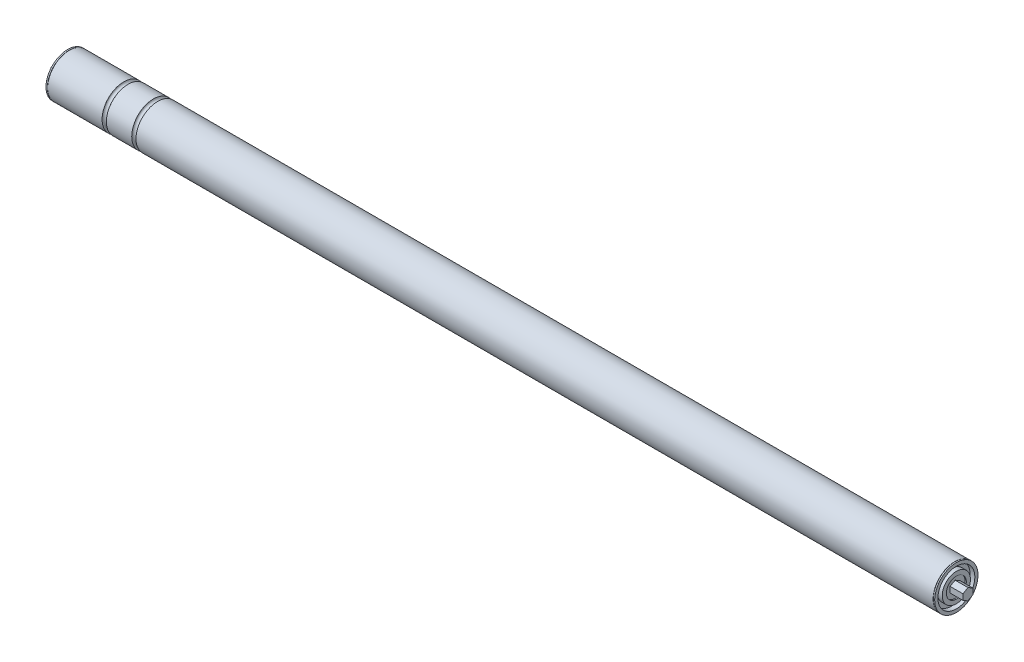
SolidWorks part; units mm, degrees
ref_plane "Front Plane" through (0, 0, 0) normal (0, 0, 1) x (1, 0, 0)
ref_plane "Top Plane" through (0, 0, 0) normal (0, 1, 0) x (1, 0, 0)
ref_plane "Right Plane" through (0, 0, 0) normal (1, 0, 0) x (0, 0, -1)
sketch "Sketch1" plane through (0, 0, 0) normal (0, 0, 1) x (1, 0, 0)
  line L0 (-493.7125, 0) -> (493.7125, 0) construction
  line L1 (493.7125, 0) -> (508, 0) construction
  line L2 (-493.7125, 0) -> (-508, 0) construction
  line L3 (0, 24.13) -> (0, -24.13) construction
  line L4 (-508, 5.5562) -> (-508, -5.5563) construction
  line L5 (508, 5.5562) -> (508, -5.5562) construction
  line L6 (-495.0969, 24.13) -> (-495.0969, -24.13) construction
  line L7 (-495.0969, 0) -> (495.0969, 0) construction
  line L8 (495.0969, 24.13) -> (495.0969, -24.13) construction
  line L9 (-430.2125, 24.13) -> (-430.2125, -24.13) construction
  line L10 (-432.5937, 21.7188) -> (-427.8312, 21.7188) construction
  line L11 (-495.3, 11.1125) -> (-495.3, -11.1125) construction
  line L12 (495.3, 11.1125) -> (495.3, -11.1125) construction
  point P2 (-495.3, 0)
  point P6 (495.3, 0)
  point P23 (-430.2125, 21.7188)
  dimension "D1" = 1.5875
  dimension "D2" = 1.5875
  dimension "BF" = 990.6
  dimension "Overall Width" = 1016
  dimension "D4" = 48.26
  dimension "D5" = 11.1125
  dimension "D6" = 990.1937
  dimension "D8" = 2.4112
  dimension "D9" = 4.7625
  dimension "D10" = 22.225
  dimension "Bearing to Groove Width" = 63.5
sketch "Sketch2" plane through (0, 0, 0) normal (0, 0, 1) x (1, 0, 0)
  line L0 (-493.7125, 0) -> (-493.7125, 11.1125)
  line L1 (-493.7125, 11.1125) -> (-495.0969, 11.1125)
  line L2 (-495.0969, 24.13) -> (-495.0969, -24.13) construction
  line L3 (-493.7125, 0) -> (-508, 0) construction
  line L4 (-495.0969, 11.1125) -> (-495.0969, 15.7129)
  line L5 (-493.7125, 0) -> (-487.9849, 0) construction
  line L6 (-493.7125, 0) -> (-487.9849, 0)
  line L7 (-495.0969, 15.7129) -> (-489.7629, 15.7129)
  line L8 (-489.7629, 15.7129) -> (-489.7629, 20.574)
  line L9 (-495.0969, 24.13) -> (-495.0969, 20.574)
  line L10 (-495.0969, 20.574) -> (-489.7629, 20.574)
  line L11 (-495.0969, 24.13) -> (-493.3189, 24.13)
  line L12 (-493.3189, 24.13) -> (-493.3189, 22.352)
  line L13 (-493.3189, 22.352) -> (-487.9849, 22.352)
  line L14 (-487.9849, 22.352) -> (-487.9849, 0)
  line L15 (-493.7125, 0) -> (493.7125, 0) construction
  line L16 (-508, 5.5562) -> (-508, -5.5563) construction
  dimension "D3" = 22.225
  dimension "D1" = 1.778
  dimension "D2" = 1.778
  dimension "D4" = 1.778
  dimension "D5" = 31.4259
  dimension "D6" = 1.778
  dimension "D7" = 5.334
revolve "Revolve1" add sketch "Sketch2" angle 360 mid plane about L5
mirror "Mirror2" about plane through (0, 0, 0) normal (1, 0, 0) of bodies 101
sketch "Sketch3" plane through (0, 0, 0) normal (1, 0, 0) x (0, 0, -1)
  circle A0 centre (0, 0) radius 24.13
  circle A1 centre (0, 0) radius 22.352 construction
  circle A2 centre (0, 0) radius 22.352 construction
extrude "Boss-Extrude1" add sketch "Sketch3" along normal up to surface (487.9849 mm away) and the other way up to surface (487.9849 mm away) up to face at (487.9849, -22.352, 0) other way up to face at (-487.9849, -22.352, 0)
chamfer "Chamfer1" distance 0.254 angle 45 2 edges at (-493.3189, -24.13, 0) (493.3189, -24.13, 0)
sketch "Sketch6" plane through (-487.9849, 0, 0) normal (-1, 0, 0) x (0, 0, 1)
  circle A0 centre (0, 0) radius 22.352 construction
  circle A1 centre (0, 0) radius 24.13
  circle A2 centre (0, 0) radius 24.13
  circle A3 centre (0, 0) radius 22.352
  dimension "D1" = 0
extrude "Boss-Extrude3" add sketch "Sketch6" along normal up to surface and the other way up to surface up to face at (-493.3189, -23.876, 0) other way up to face at (493.3189, 23.876, 0)
sketch "Sketch4" plane through (0, 0, 0) normal (1, 0, 0) x (0, 0, -1)
  line L1 (0, 6.4158) -> (-5.5563, 3.2079)
  line L2 (-5.5563, 3.2079) -> (-5.5563, -3.2079)
  line L3 (-5.5563, -3.2079) -> (0, -6.4158)
  line L4 (0, -6.4158) -> (5.5562, -3.2079)
  line L5 (5.5562, -3.2079) -> (5.5562, 3.2079)
  line L6 (5.5562, 3.2079) -> (0, 6.4158)
  circle A0 centre (0, 0) radius 5.5563 construction
  dimension "D1" = 11.1125
extrude "Boss-Extrude2" add sketch "Sketch4" along normal up to vertex and the other way up to vertex up to point (508, 0, 0) other way up to point (-508, 0, 0)
sketch "Sketch5" plane through (0, 0, 0) normal (0, 0, 1) x (1, 0, 0)
  line L0 (-432.5937, 21.7188) -> (-427.8312, 21.7188) construction
  line L1 (-430.2125, 24.13) -> (-430.2125, -24.13) construction
  line L2 (-432.5937, 21.7188) -> (-432.5937, 25.5224) construction
  line L3 (-508, 0) -> (-493.7125, 0) construction
  line L7 (-430.2125, 24.1) -> (-432.5937, 24.1) construction
  line L8 (-433.3811, 24.8874) -> (-433.3811, 25.5224)
  line L9 (-433.3811, 25.5224) -> (-427.0439, 25.5224)
  line L10 (-427.0439, 24.8874) -> (-427.0439, 25.5224)
  arc A0 (-432.5937, 24.1) -> (-427.8313, 24.1) centre (-430.2125, 24.1) ccw
  arc A1 (-427.8313, 24.1) -> (-427.0439, 24.8874) centre (-427.0439, 24.1) cw
  arc A2 (-432.5937, 24.1) -> (-433.3811, 24.8874) centre (-433.3811, 24.1) ccw
  dimension "D2" = 0.7874
  dimension "D1" = 0.03
  dimension "D3" = 0.635
revolve "Cut-Revolve1" cut sketch "Sketch5" angle 360 mid plane about L3
pattern_linear "LPattern1" count 2 spacing 33.02 along (1, 0, 0) of "Cut-Revolve1"
ref_axis "Center Axis 1" through (307.34, 0, 0) along (-1, 0, 0)
ref_plane "Contact Plane 1" through (-508, 0, 0) normal (-1, 0, 0) x (0, 0, 1)
ref_plane "Contact Plane 2" through (-493.7125, 0, 0) normal (-1, 0, 0) x (0, 0, 1)
equation "\"D6@Sketch1\" = \"BF@Sketch1\"-.40625"
equation "\"D3@Sketch2\" = \"D5@Sketch1\"*2"
equation "\"D10@Sketch1\" = \"D3@Sketch2\""
equation "\"D2@Sketch2\" = \"D1@Sketch2\""
equation "\"D4@Sketch2\" = \"D2@Sketch2\""
equation "\"D6@Sketch2\" = \"D1@Sketch2\""
equation "\"D7@Sketch2\" = \"D1@Sketch2\"*3"
equation "\"D8@Sketch1\"=(\"D9@Sketch1\"/2)+.030"
